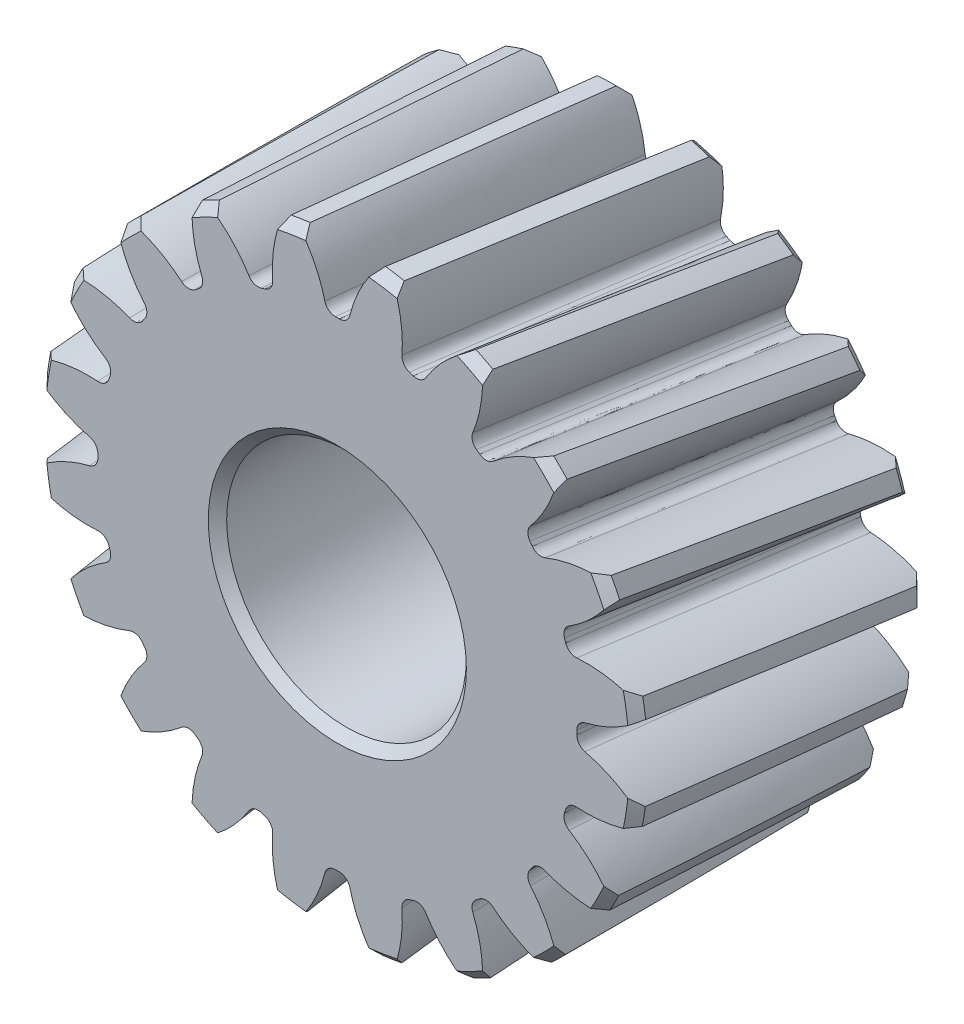
SolidWorks part; units mm, degrees
ref_plane "Front Plane" through (0, 0, 0) normal (0, 0, 1) x (1, 0, 0)
ref_plane "Top Plane" through (0, 0, 0) normal (0, 1, 0) x (1, 0, 0)
ref_plane "Right Plane" through (0, 0, 0) normal (1, 0, 0) x (0, 0, -1)
sketch "Sketch1" plane through (0, 0, 0) normal (0, 0, 1) x (1, 0, 0)
  line L0 (0, 0) -> (0, 2) construction
  line L1 (-0.6428, 2.234) -> (0.6428, 1.766) construction
  circle A0 centre (0, 0) radius 1.75 construction
  circle A1 centre (0, 0) radius 2.2 construction
  circle A2 centre (0, 0) radius 2 construction
  circle A3 centre (0, 0) radius 1.8794 construction
  circle A5 centre (0, 0) radius 0.875 construction
  point P8 (0.1, 0)
  point P13 (10, 0)
  dimension "OD" = 4.4
  dimension "Root Diameter" = 3.5
  dimension "Gear Pitch Diameter" = 4
  dimension "Base Diameter" = 3.7588
  dimension "For Shaft Diameter" = 1.75
  dimension "Pressure Angle" = 20
  dimension "Number of Teeth" = 20
  dimension "Module" = 0.2
sketch "Sketch2" plane through (0, 0, 0) normal (1, 0, 0) x (0, 0, -1)
  line L0 (-1.05, 0) -> (1.05, 0) construction
  line L1 (1.05, 2.2) -> (1.05, -2.2) construction
  line L3 (-1.05, 2.2) -> (1.05, 2.2) construction
  line L4 (0, 12.5) -> (0, -12.5) construction
  line L5 (-1.05, 12.5) -> (-1.05, -12.5) construction
  line L6 (0, 2.4977) -> (0, -2.4977) construction
  point P2 (0, 2.2)
  dimension "Overall Width" = 2.1
  dimension "Face Width" = 1.05
sketch "Sketch3" plane through (0, 0, 0) normal (0, 0, 1) x (1, 0, 0)
  circle A0 centre (0, 0) radius 2.2
  circle A1 centre (0, 0) radius 2.2 construction
extrude "Boss-Extrude1" add sketch "Sketch3" against normal up to vertex (1.05 mm away) and the other way up to vertex (1.05 mm away) up to point (0, 0, -1.05) other way up to point (0, 0, 1.05)
sketch "Sketch5" plane through (0, 0, 0) normal (1, 0, 0) x (0, 0, -1)
  line L5 (-1.05, 0) -> (1.05, 0)
  line L6 (-1.05, 0) -> (-1.05, 0.875)
  line L7 (-1.05, 0.875) -> (1.05, 0.875)
  line L8 (1.05, 0) -> (1.05, 0.875)
  point P12 (0, 0.875)
revolve "Cut-Revolve1" cut sketch "Sketch5" angle 360 about L0
chamfer "Chamfer2" distance 0.0671 angle 45 4 edges at (2.2, 0, -1.05) (0.875, 0, -1.05) (0.875, 0, 1.05) (2.2, 0, 1.05)
sketch "Sketch4" plane through (0, 0, 0) normal (0, 0, 1) x (1, 0, 0)
  line L0 (1.7482, -0.0785) -> (1.7482, 0.0785)
  arc A3 (2.1827, 0.2754) -> (2.1827, -0.2754) centre (0, 0) cw
  circle A4 centre (0, 0) radius 2.2 construction
  arc A5 (2.1827, 0.2754) -> (1.7482, 0.0785) centre (1.5748, 1.0393) cw
  circle A6 centre (0, 0) radius 1.75 construction
  arc A7 (2.1827, -0.2754) -> (1.7482, -0.0785) centre (1.5748, -1.0393) ccw
  spline S0 degree 4 poles (1.8756, 0.1195) (1.8761, 0.1196) (1.8775, 0.1197) (1.8802, 0.12) (1.8847, 0.1207) (1.8903, 0.1217) (1.8975, 0.1231) (1.906, 0.1251) (1.9152, 0.1276) (1.9253, 0.1305) (1.9353, 0.1337) (1.9452, 0.1371) (1.955, 0.1407) (1.9669, 0.1453) (1.981, 0.1511) (1.9974, 0.1584) (2.0159, 0.1673) (2.0346, 0.177) (2.0529, 0.187) (2.0712, 0.1976) (2.0888, 0.2084) (2.1068, 0.2201) (2.1235, 0.2312) (2.1417, 0.2442) (2.1567, 0.2551) (2.1798, 0.2729) (2.1896, 0.2808) (2.2043, 0.2929) (2.2092, 0.2971) knots 0 0 0 0 0 0.005377 0.015084 0.028532 0.04661 0.064855 0.092111 0.119476 0.146842 0.174209 0.201575 0.228941 0.256307 0.307035 0.361767 0.4165 0.471232 0.525964 0.580697 0.635429 0.690161 0.744894 0.799626 0.854358 0.909091 1 1 1 1 1 construction
  spline S1 degree 4 poles (1.8756, 0.1195) (1.8761, 0.1196) (1.8775, 0.1197) (1.8802, 0.12) (1.8847, 0.1207) (1.8903, 0.1217) (1.8975, 0.1231) (1.906, 0.1251) (1.9152, 0.1276) (1.9253, 0.1305) (1.9353, 0.1337) (1.9452, 0.1371) (1.955, 0.1407) (1.9669, 0.1453) (1.981, 0.1511) (1.9974, 0.1584) (2.0159, 0.1673) (2.0346, 0.177) (2.0529, 0.187) (2.0712, 0.1976) (2.0888, 0.2084) (2.1068, 0.2201) (2.1235, 0.2312) (2.1417, 0.2442) (2.1567, 0.2551) (2.1716, 0.2666) (2.179, 0.2724) (2.1827, 0.2754) knots 0 0 0 0 0 0.005377 0.015084 0.028532 0.04661 0.064855 0.092111 0.119476 0.146842 0.174209 0.201575 0.228941 0.256307 0.307035 0.361767 0.4165 0.471232 0.525964 0.580697 0.635429 0.690161 0.744894 0.799626 0.854358 0.909091 0.909091 0.909091 0.909091 0.909091 construction
  spline S2 degree 4 poles (1.8756, -0.1195) (1.8761, -0.1196) (1.8775, -0.1197) (1.8802, -0.12) (1.8847, -0.1207) (1.8903, -0.1217) (1.8975, -0.1231) (1.906, -0.1251) (1.9152, -0.1276) (1.9253, -0.1305) (1.9353, -0.1337) (1.9452, -0.1371) (1.955, -0.1407) (1.9669, -0.1453) (1.981, -0.1511) (1.9974, -0.1584) (2.0159, -0.1673) (2.0346, -0.177) (2.0529, -0.187) (2.0712, -0.1976) (2.0888, -0.2084) (2.1068, -0.2201) (2.1235, -0.2312) (2.1417, -0.2442) (2.1567, -0.2551) (2.1798, -0.2729) (2.1896, -0.2808) (2.2043, -0.2929) (2.2092, -0.2971) knots 0 0 0 0 0 0.005377 0.015084 0.028532 0.04661 0.064855 0.092111 0.119476 0.146842 0.174209 0.201575 0.228941 0.256307 0.307035 0.361767 0.4165 0.471232 0.525964 0.580697 0.635429 0.690161 0.744894 0.799626 0.854358 0.909091 1 1 1 1 1 construction
  spline S3 degree 4 poles (1.8756, -0.1195) (1.8761, -0.1196) (1.8775, -0.1197) (1.8802, -0.12) (1.8847, -0.1207) (1.8903, -0.1217) (1.8975, -0.1231) (1.906, -0.1251) (1.9152, -0.1276) (1.9253, -0.1305) (1.9353, -0.1337) (1.9452, -0.1371) (1.955, -0.1407) (1.9669, -0.1453) (1.981, -0.1511) (1.9974, -0.1584) (2.0159, -0.1673) (2.0346, -0.177) (2.0529, -0.187) (2.0712, -0.1976) (2.0888, -0.2084) (2.1068, -0.2201) (2.1235, -0.2312) (2.1417, -0.2442) (2.1567, -0.2551) (2.1716, -0.2666) (2.179, -0.2724) (2.1827, -0.2754) knots 0 0 0 0 0 0.005377 0.015084 0.028532 0.04661 0.064855 0.092111 0.119476 0.146842 0.174209 0.201575 0.228941 0.256307 0.307035 0.361767 0.4165 0.471232 0.525964 0.580697 0.635429 0.690161 0.744894 0.799626 0.854358 0.909091 0.909091 0.909091 0.909091 0.909091 construction
  dimension "D1" = 0.1571
sketch "Sketch6" plane through (0, 0, 1.05) normal (0, 0, 1) x (1, 0, 0)
  circle A0 centre (0, 0) radius 2.2 construction
  circle A1 centre (0, 0) radius 2.2
curve "Helix/Spiral1" pitch 100 height 5 radius 2.2 centre (0, 0, 1.05) axis (0, 0, -1) start towards (1, 0, 0)
sketch "Sketch7" plane through (0, 0, 1.05) normal (0, 0, 1) x (1, 0, 0)
  line L1 (1.7482, 0.0785) -> (1.7482, -0.0785)
  line L2 (1.7482, 0.0785) -> (1.7482, -0.0785)
  arc A3 (1.7482, 0.0785) -> (2.1827, 0.2754) centre (1.5748, 1.0393) ccw
  arc A4 (2.1827, -0.2754) -> (2.1827, 0.2754) centre (0, 0) ccw
  arc A5 (2.1827, -0.2754) -> (1.7482, -0.0785) centre (1.5748, -1.0393) ccw
  arc A6 (1.7482, 0.0785) -> (2.1827, 0.2754) centre (1.5748, 1.0393) ccw
  arc A7 (2.1827, -0.2754) -> (2.1827, 0.2754) centre (0, 0) ccw
  arc A8 (2.1827, -0.2754) -> (1.7482, -0.0785) centre (1.5748, -1.0393) ccw
  dimension "D1" = 0
sweep "Cut-Sweep1" cut profiles "Sketch7" path "Helix/Spiral1"
fillet "Fillet1" radius 0.0785 2 edges
pattern_circular "CirPattern1" count 20 over 360 about axis through (0, 0, -1.05) along (0, 0, 1) of "Cut-Sweep1", "Fillet1"
equation "\"Number of Teeth\"= 20"
equation "\"Module\"= 0.2"
equation "\"Diametral Pitch\"= 1 / \"Module\""
equation "\"Dedendum\"= 1.25 / \"Diametral Pitch\""
equation "\"Pitch Diameter\"= \"Module\" * \"Number of Teeth\""
equation "\"Root Diameter\"= \"Pitch Diameter\" - ( 2 * \"Dedendum\" )"
equation "\"Root Diameter@Sketch1\"=\"Root Diameter\""
equation "\"OD@Sketch1\" = \"Outside Diameter\""
equation "\"D1@CirPattern1\"= \"Number of Teeth\""
equation "\"Pressure Angle\"= 20"
equation "\"Base Diameter\"= \"Pitch Diameter\" * cos ( \"Pressure Angle\" )"
equation "\"Outside Diameter\"= ( \"Number of Teeth\" + 2 ) / \"Diametral Pitch\""
equation "\"Pitch Angle\"= 360deg / \"Number of Teeth\""
equation "\"Alpha\"= sqr ( \"Pitch Diameter\" ^ 2 - \"Base Diameter\" ^ 2 ) / \"Base Diameter\" * 180 / PI - \"Pressure Angle\""
equation "\"Beta\"= ( \"Pitch Angle\" / 4 - \"Alpha\" )"
equation "\"Phi\"= sqr ( ( \"Outside Diameter\" / 2 ) ^ 2 - ( \"Base Diameter\" / 2 ) ^ 2 ) / ( \"Base Diameter\" / 2 )"
equation "\"Addendum\"= 1 / \"Diametral Pitch\""
equation "\"WorkingDepth\"= 2 / \"Diametral Pitch\""
equation "\"WholeDepth\"= 2.25 / \"Diametral Pitch\""
equation "\"Clearance\"= 0.25 / \"Diametral Pitch\""
equation "\"ToothThickness\"= ( pi * 2 ) / \"Diametral Pitch\""
equation "\"CircularPitch\"= pi / \"Diametral Pitch\""
equation "\"Number of Teeth@Sketch1\"=\"Number of Teeth\""
equation "\"Module@Sketch1\"=\"Module\""
equation "\"Pressure Angle@Sketch1\"=\"Pressure Angle\""
equation "\"Gear Pitch Diameter@Sketch1\"=\"Pitch Diameter\""
equation "\"Base Diameter@Sketch1\"=\"Base Diameter\""
equation "\"Fillet\"= \"Clearance\" * cos ( \"Pressure Angle\" ) * tan ( ( 90 + \"Pressure Angle\" ) / 2 )"
equation "\"D1\"= \"Fillet\""
equation "\"D1\"= \"Set Screw Pitch@Sketch1\" * .75"
equation "\"D1\"= \"Set Screw Diameter@Sketch1\" / 2"
equation "\"D3\"= \"Set Screw Pitch@Sketch1\" +  ( \"Hub Diameter@Sketch1\" / 2 ) "
equation "\"D4\"= \"Set Screw Pitch@Sketch1\""
equation "\"D2\"= \"Fillet\" * 2"
equation "\"D1\"= \"Fillet\" * 2"
equation "\"D1@Chamfer2\"=\"Fillet\""
equation "\"D1@Sketch4\"=\"CircularPitch\"*0.25"
equation "\"D1@Fillet1\"=\"CircularPitch\"*0.125"
